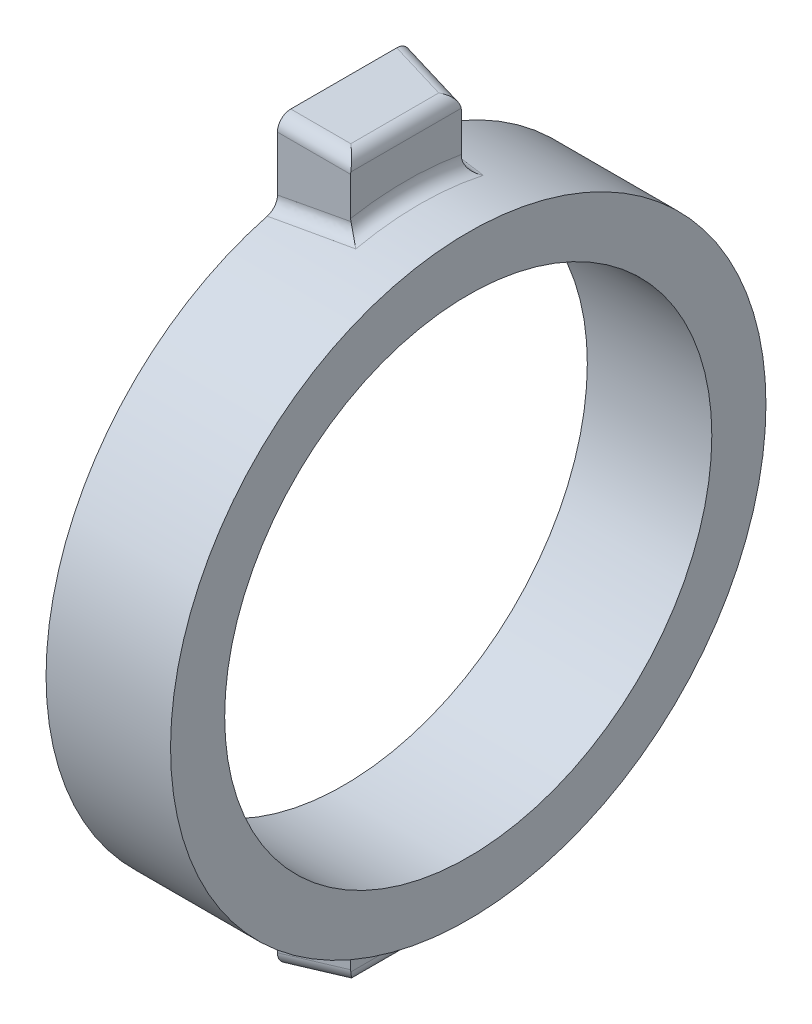
SolidWorks part; units mm, degrees
material "ABS"
ref_plane "Front Plane" through (0, 0, 0) normal (1, 0, 0) x (0, 1, 0)
ref_plane "Top Plane" through (0, 0, 0) normal (0, 0, 1) x (0, 1, 0)
ref_plane "Right Plane" through (0, 0, 0) normal (0, 1, 0) x (-1, 0, 0)
sketch "Sketch1" plane through (0, 0, 0) normal (1, 0, 0) x (0, 1, 0)
  circle A0 centre (0, 0) radius 11
  circle A1 centre (0, 0) radius 11
  circle A2 centre (0, 0) radius 9
  dimension "D1" = 22
  dimension "D2" = 22
  dimension "D3" = 2
extrude "Boss-Extrude1" add sketch "Sketch1" along normal blind 4.6 contours A0 A1 region at (0, -10.6889, 0)
extrude "Boss-Extrude2" add sketch "Sketch1<3>" along normal blind 4.6 contours A1 A2 region at (0, -10.6889, 0)
sketch "Sketch1<3>" plane through (0, 0, 0) normal (1, 0, 0) x (0, 1, 0) same geometry as "Sketch1"
sketch "Sketch2" plane through (0, 0, 0) normal (-1, 0, 0) x (0, -1, 0)
  line L0 (-13.6237, -2.45) -> (-10.7237, -2.45)
  line L1 (-10.7237, -2.45) -> (-8.6601, -2.45)
  line L2 (-13.6237, 2.45) -> (-10.7237, 2.45)
  line L3 (-10.7237, 2.45) -> (-8.6601, 2.45)
  line L4 (-13.6237, 2.45) -> (-13.6237, -2.45)
  line L5 (0, 0) -> (-13.6237, 0) construction
  line L6 (0, 0) -> (0, 8.075) construction
  line L7 (10.7237, -2.45) -> (8.6601, -2.45)
  line L8 (13.6237, -2.45) -> (10.7237, -2.45)
  line L9 (13.6237, 2.45) -> (13.6237, -2.45)
  line L10 (13.6237, 2.45) -> (10.7237, 2.45)
  line L11 (10.7237, 2.45) -> (8.6601, 2.45)
  circle A0 centre (0, 0) radius 11 construction
  arc A3 (-8.6601, 2.45) -> (-8.6601, -2.45) centre (0, 0) ccw
  arc A4 (8.6601, -2.45) -> (8.6601, 2.45) centre (0, 0) ccw
  circle A8 centre (0, 0) radius 9 construction
  dimension "D1" = 4.9
  dimension "D2" = 2.9
extrude "Boss-Extrude3" add sketch "Sketch2" against normal blind 2.3 draft 10
fillet "Fillet1" radius 0.5 12 edges at (1.1477, -10.7679, 2.2476) (2.3, -13.2181, 0) (1.15, -13.4209, 2.2472) (1.15, -13.4209, -2.2472) (1.1477, -10.7679, -2.2476) (2.3, -11, 0) (1.15, 13.4209, 2.2472) (1.15, 13.4209, -2.2472) (1.1477, 10.7679, -2.2476) (1.1477, 10.7679, 2.2476) (2.3, 13.2181, 0) (2.3, 11, 0)
